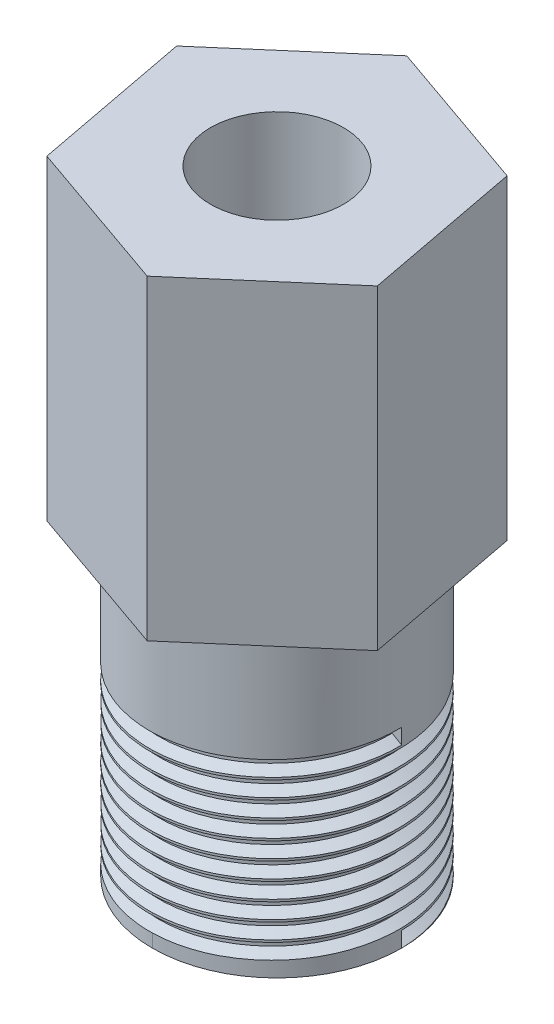
SolidWorks part; units mm, degrees
ref_plane "Front Plane" through (0, 0, 0) normal (0, 0, 1) x (1, 0, 0)
ref_plane "Top Plane" through (0, 0, 0) normal (0, 1, 0) x (1, 0, 0)
ref_plane "Right Plane" through (0, 0, 0) normal (1, 0, 0) x (0, 0, -1)
sketch "Szkic1" plane through (0, 0, 0) normal (0, 0, 1) x (1, 0, 0)
  line L0 (0, 0) -> (-7.5, 0)
  line L1 (-7.5, 0) -> (-7.5, 12)
  line L2 (-7.5, 12) -> (0, 12)
  line L3 (0, 12) -> (0, 0)
  line L4 (-7.5, 12) -> (-7.5, 16)
  line L5 (-7.5, 16) -> (0, 16)
  line L6 (0, 16) -> (0, 12)
  line L7 (-7.5, 16) -> (-7.5, 37)
  line L8 (-7.5, 37) -> (-4, 37)
  line L9 (-4, 37) -> (-4, 16)
  line L10 (-7.5, 12) -> (-7.5, 16)
  line L12 (-7.5, 12) -> (0, 12)
  line L13 (-7.5, 12) -> (-7.5, 16)
  line L14 (-7.5, 16) -> (0, 16)
  line L15 (0, 12) -> (0, 16)
  line L16 (-7.5, 16) -> (-4, 16)
  line L17 (-7.5, 16) -> (-7.5, 37)
  line L18 (-7.5, 37) -> (-4, 37)
  line L19 (-4, 16) -> (-4, 37)
  dimension "D1" = 7.5
  dimension "D2" = 4
  dimension "D3" = 12
  dimension "D4" = 4
  dimension "D5" = 37
revolve "Obrót1" add sketch "Szkic1" angle 360 about L3 region at (-3.75, 6, 0) region at (-3.75, 14, 0) region at (-5.75, 26.5, 0)
sketch "Szkic2" plane through (0, 37, 0) normal (0, 1, 0) x (1, 0, 0)
  line L1 (-9.2675, 3.2321) -> (-7.4328, -6.4099)
  line L2 (-7.4328, -6.4099) -> (1.8347, -9.6419)
  line L3 (1.8347, -9.6419) -> (9.2675, -3.2321)
  line L4 (9.2675, -3.2321) -> (7.4328, 6.4099)
  line L5 (7.4328, 6.4099) -> (-1.8347, 9.6419)
  line L6 (-1.8347, 9.6419) -> (-9.2675, 3.2321)
  circle A0 centre (0, 0) radius 8.5 construction
  circle A1 centre (0, 0) radius 4
  dimension "D1" = 17
extrude "Dodanie-wyciągnięcie1" add sketch "Szkic2" against normal blind 19
thread "Gwint1" pitch 1.0583 method cut profile "Thread Profile1" start angle 0, offset 0, length 0, pitch 1.0583, diameter 15
ref_plane "Płaszczyzna1" through (7.5, 0, 0) normal (0, 0, 1) x (1, 0, 0)
sketch "Thread Profile1" plane through (7.5, 0, 0) normal (0, 0, 1) x (1, 0, 0)
  line L0 (0, 0) -> (0, 1.0583) construction
  line L11 (0, 0) -> (0, 0.926)
  line L12 (0, 0.926) -> (-0.5728, 0.5953)
  line L13 (-0.5728, 0.5953) -> (-0.5728, 0.3307)
  line L15 (-0.5728, 0.3307) -> (0, 0)
  line L17 (-0.5728, 0.463) -> (0, 0.463) construction
  point P2 (0, 0)
  dimension "Pitch" = 1.0583
  dimension "Profile_Angle" = 60
  dimension "Profile_Land" = 0.2646
  dimension "Profile_Height" = 0.5728
extrude "Wytnij-wyciągnięcie1" cut sketch "Szkic2<4>" against normal blind 91 contours A1
sketch "Szkic2<4>" plane through (0, 37, 0) normal (0, 1, 0) x (1, 0, 0) same geometry as "Szkic2"
